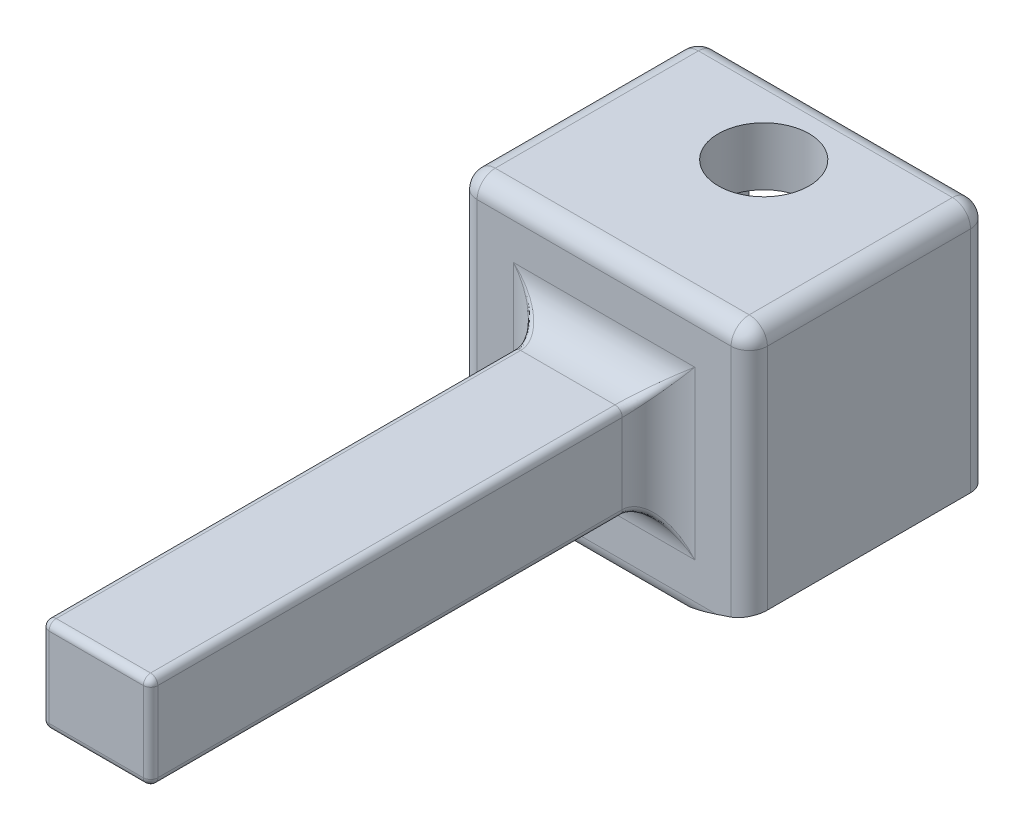
SolidWorks part; units mm, degrees
ref_plane "Front Plane" through (0, 0, 0) normal (0, 0, 1) x (1, 0, 0)
ref_plane "Top Plane" through (0, 0, 0) normal (0, 1, 0) x (1, 0, 0)
ref_plane "Right Plane" through (0, 0, 0) normal (1, 0, 0) x (0, 0, -1)
sketch "Sketch1" plane through (0, 0, 0) normal (0, 0, 1) x (1, 0, 0)
  line L0 (-4.318, -3.81) -> (4.318, -3.81)
  line L1 (-5.08, 4.826) -> (5.08, 4.826)
  line L2 (-5.08, 4.826) -> (-5.08, -4.826)
  line L3 (-5.08, -4.826) -> (5.08, -4.826)
  line L4 (5.08, 4.826) -> (5.08, -4.826)
  line L5 (-5.08, 4.826) -> (5.08, -4.826) construction
  line L6 (-5.08, -4.826) -> (5.08, 4.826) construction
  line L7 (4.318, -3.81) -> (4.318, -1.016)
  line L8 (4.318, -1.016) -> (3.302, -1.016)
  line L9 (3.302, -1.016) -> (3.302, 2.794)
  line L10 (3.302, 2.794) -> (-3.302, 2.794)
  line L11 (-3.302, 2.794) -> (-3.302, -1.016)
  line L12 (-3.302, -1.016) -> (-4.318, -1.016)
  line L13 (-4.318, -1.016) -> (-4.318, -3.81)
  point P5 (0, 2.794)
  point P7 (0, 0)
  dimension "D1" = 0.762
  dimension "D2" = 2.032
  dimension "D3" = 1.016
  dimension "D4" = 6.604
  dimension "D5" = 3.81
  dimension "D6" = 6.604
  dimension "D7" = 8.636
extrude "Boss-Extrude1" add sketch "Sketch1" along normal blind 7.112
sketch "Sketch2" plane through (0, 4.826, 0) normal (0, 1, 0) x (1, 0, 0)
  line L1 (5.08, 0) -> (-5.08, 0) construction
  circle A0 centre (0, -2.794) radius 1.5875
  dimension "D1" = 3.175
  dimension "D2" = 2.794
extrude "Cut-Extrude1" cut sketch "Sketch2" against normal through all both and the other way through all
sketch "Sketch3" plane through (0, 0, 7.112) normal (0, 0, 1) x (1, 0, 0)
  line L1 (-5.08, 4.826) -> (5.08, 4.826)
  line L2 (-5.08, 4.826) -> (-5.08, -4.826)
  line L3 (-5.08, -4.826) -> (5.08, -4.826)
  line L4 (5.08, 4.826) -> (5.08, -4.826)
sketch "Sketch7" plane through (0, 0, 7.112) normal (0, 0, 1) x (1, 0, 0)
  line L0 (-5.08, 4.826) -> (5.08, 4.826)
  line L1 (5.08, 4.826) -> (5.08, -4.826)
  line L2 (5.08, -4.826) -> (-5.08, -4.826)
  line L3 (-5.08, -4.826) -> (-5.08, 4.826)
extrude "Boss-Extrude3" add sketch "Sketch7" along normal blind 1.27
fillet "Fillet1" radius 0.635 3 edges at (-5.08, 0, 0) (0, 4.826, 0) (5.08, 0, 0)
fillet "Fillet3" radius 0.635 13 edges at (-5.08, 4.826, 4.5085) (5.08, 4.826, 4.5085) (-5.08, -4.826, 4.5085) (5.08, -4.826, 4.5085) (-4.894, 4.64, 0.186) (4.894, 4.64, 0.186) (-4.894, -4.826, 0.186) (0, -4.826, 0) (4.894, -4.826, 0.186) (0, 4.826, 8.382) (5.08, 0, 8.382) (0, -4.826, 8.382) (-5.08, 0, 8.382)
fillet "Fillet4" radius 0.381 2 edges at (-3.302, -1.016, 3.556) (3.302, -1.016, 3.556)
sketch "Sketch11" plane through (4.318, 0, 0) normal (-1, 0, 0) x (0, 0, 1)
  line L0 (0, -3.81) -> (5.08, -3.81)
  line L1 (5.08, -3.81) -> (5.08, -4.064)
  line L2 (0, -3.81) -> (0, -4.826)
  line L3 (0, -4.826) -> (10.16, -4.826)
  line L4 (7.747, -4.826) -> (0.635, -4.826) construction
  line L5 (10.16, -4.826) -> (5.08, -4.064)
  dimension "D1" = 0.254
  dimension "D2" = 5.08
  dimension "D3" = 10.16
extrude "Cut-Extrude3" cut sketch "Sketch11" against normal through all both and the other way through all
fillet "Fillet9" radius 0.254 3 edges at (0, -3.81, 7.112) (-4.318, -3.81, 6.096) (4.318, -3.81, 6.096)
sketch "Sketch13" plane through (0, 0, 5.08) normal (0, 0, -1) x (-1, 0, 0)
  line L0 (-5.08, -3.81) -> (-5.08, -4.826)
  line L1 (-5.08, -4.826) -> (-2.032, -4.826)
  line L2 (5.08, -4.826) -> (-5.08, -4.826) construction
  line L3 (-4.318, -3.81) -> (-4.318, -4.064) construction
  line L4 (-5.08, -4.064) -> (5.08, -4.064) construction
  line L5 (-5.08, -3.81) -> (-2.032, -4.826)
  line L6 (5.08, -3.81) -> (5.08, -4.826)
  line L7 (5.08, -4.826) -> (2.032, -4.826)
  line L8 (4.318, -3.81) -> (4.318, -4.064) construction
  line L9 (5.08, -3.81) -> (2.032, -4.826)
extrude "Cut-Extrude7" cut sketch "Sketch13" against normal through all
sketch "Sketch14" plane through (0, 0, 8.382) normal (0, 0, 1) x (1, 0, 0)
  line L8 (-1.905, 1.651) -> (-1.905, -1.651)
  line L9 (-1.905, 1.651) -> (-1.905, -1.651)
  line L10 (-1.905, -1.651) -> (1.905, -1.651)
  line L11 (-1.905, -1.651) -> (1.905, -1.651)
  line L12 (1.905, -1.651) -> (1.905, 1.651)
  line L13 (1.905, -1.651) -> (1.905, 1.651)
  line L14 (1.905, 1.651) -> (-1.905, 1.651)
  line L15 (1.905, 1.651) -> (-1.905, 1.651)
  dimension "D1" = 2.54
extrude "Boss-Extrude4" add sketch "Sketch14" along normal blind 17.78
fillet "Fillet14" radius 1.27 4 edges at (-1.905, 0, 8.382) (0, -1.651, 8.382) (1.905, 0, 8.382) (0, 1.651, 8.382)
fillet "Fillet15" radius 0.254 12 edges at (2.277, -2.023, 8.754) (-2.277, -2.023, 8.754) (-2.277, 2.023, 8.754) (2.277, 2.023, 8.754) (1.905, 0, 26.162) (1.905, -1.651, 17.907) (-1.905, 0, 26.162) (0, -1.651, 26.162) (0, 1.651, 26.162) (-1.905, -1.651, 17.907) (-1.905, 1.651, 17.907) (1.905, 1.651, 17.907)
